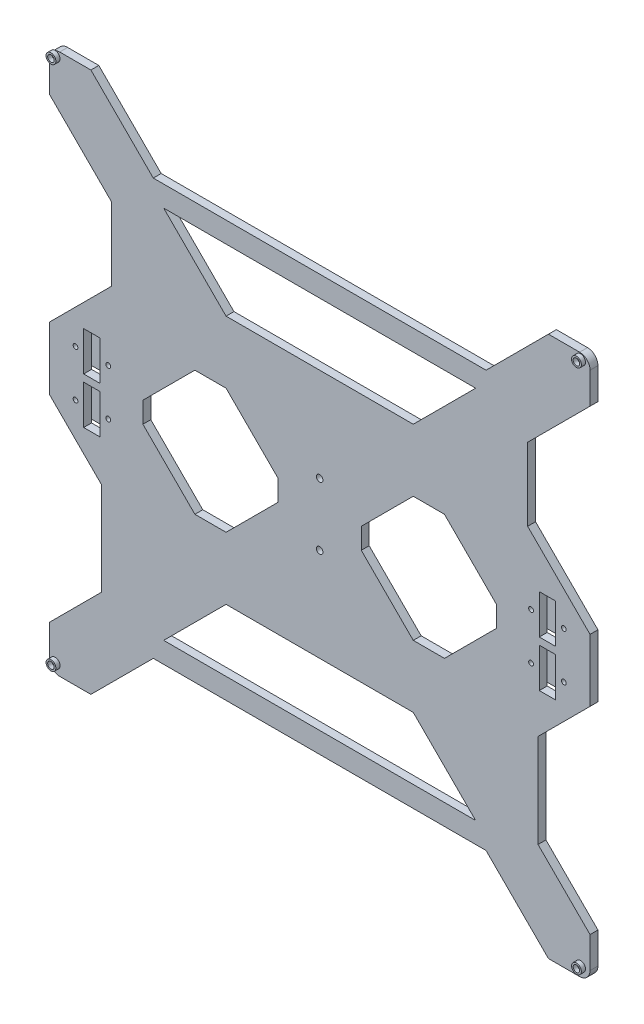
SolidWorks part; units mm, degrees
material "5052-H32"
ref_plane "Front Plane" through (0, 0, 0) normal (0, 0, 1) x (1, 0, 0)
ref_plane "Top Plane" through (0, 0, 0) normal (0, 1, 0) x (1, 0, 0)
ref_plane "Right Plane" through (0, 0, 0) normal (1, 0, 0) x (0, 0, -1)
sketch "Model" plane through (0, 0, 0) normal (0, 0, 1) x (1, 0, 0)
  line L0 (38.5361, 132.6139) -> (38.5361, 132.4727)
  line L1 (38.5361, -178.6774) -> (38.5361, -178.7219)
  line L2 (-253.5639, -197.5861) -> (-253.5639, -197.7273)
  line L3 (-252.5813, 70.3317) -> (-252.5813, 25.8817)
  line L4 (-258.9313, -82.0683) -> (-258.9313, -139.2183)
  line L5 (38.5361, 132.6139) -> (38.5361, 132.4727)
  line L6 (38.5361, -178.6774) -> (38.5361, -178.7219)
  line L7 (7.7687, -139.2183) -> (7.7687, -82.0683)
  line L8 (1.4187, 25.8817) -> (1.4187, 70.3317)
  line L9 (-23.9813, 95.7317) -> (-227.1813, 95.7317)
  line L10 (-290.6813, 108.4317) -> (-252.5813, 70.3317)
  line L11 (-30.3313, -145.5683) -> (-68.4313, -107.4683)
  line L12 (-23.9813, -158.2683) -> (14.1187, -196.3683)
  line L13 (39.5187, 108.4317) -> (39.5187, 127.4817)
  line L14 (-227.1813, 95.7317) -> (-265.2813, 133.8317)
  line L15 (-220.8313, 83.0317) -> (-182.7313, 44.9317)
  line L16 (-274.6813, -45.4288) -> (-254.6813, -45.4288) construction
  line L17 (39.5187, -170.9683) -> (7.7687, -139.2183)
  line L18 (-265.2813, -196.3683) -> (-227.1813, -158.2683)
  line L19 (-182.7313, -107.4683) -> (-68.4313, -107.4683)
  line L20 (-264.6813, -45.4288) -> (-264.6813, -43.5832) construction
  line L21 (1.4187, 70.3317) -> (39.5187, 108.4317)
  line L22 (-23.9813, 95.7317) -> (14.1187, 133.8317)
  line L23 (-30.3313, 83.0317) -> (-68.4313, 44.9317)
  line L25 (-258.9313, -139.2183) -> (-290.6813, -170.9683)
  line L26 (-182.7313, 44.9317) -> (-68.4313, 44.9317)
  line L27 (-220.8313, -145.5683) -> (-182.7313, -107.4683)
  line L28 (-220.8313, -145.5683) -> (-30.3313, -145.5683)
  line L29 (-258.9313, -82.0683) -> (-290.6813, -50.3183)
  line L30 (-290.6813, -12.2183) -> (-290.6813, -50.3183)
  line L31 (-274.6813, -43.9683) -> (-274.6813, -31.2683) construction
  line L32 (-290.6813, -12.2183) -> (-252.5813, 25.8817)
  line L33 (-201.7813, -69.3683) -> (-233.5313, -37.6183)
  line L34 (-182.7313, -69.3683) -> (-201.7813, -69.3683)
  line L35 (1.4187, 25.8817) -> (39.5187, -12.2183)
  line L36 (39.5187, -12.2183) -> (39.5187, -50.3183)
  line L37 (-150.9813, -37.6183) -> (-182.7313, -69.3683)
  line L38 (39.5187, -50.3183) -> (22.4579, -67.3791)
  line L39 (22.4579, -67.3791) -> (7.7687, -82.0683)
  line L40 (-100.1813, -37.6183) -> (-100.1813, -24.9183)
  line L41 (-150.9813, -37.6183) -> (-150.9813, -24.9183)
  line L42 (-150.9813, -24.9183) -> (-182.7313, 6.8317)
  line L43 (-182.7313, 6.8317) -> (-201.7813, 6.8317)
  line L44 (-201.7813, 6.8317) -> (-233.5313, -24.9183)
  line L45 (-233.5313, -24.9183) -> (-233.5313, -37.6183)
  line L46 (-17.6313, -24.9183) -> (-17.6313, -37.6183)
  line L47 (-49.3813, 6.8317) -> (-17.6313, -24.9183)
  line L48 (-220.8313, 83.0317) -> (-30.3313, 83.0317)
  line L49 (-68.4313, 6.8317) -> (-49.3813, 6.8317)
  line L50 (-100.1813, -24.9183) -> (-68.4313, 6.8317)
  line L51 (-100.1813, -37.6183) -> (-68.4313, -69.3683)
  line L52 (-68.4313, -69.3683) -> (-49.3813, -69.3683)
  line L53 (-49.3813, -69.3683) -> (-17.6313, -37.6183)
  line L58 (-265.2813, -196.3683) -> (-284.3313, -196.3683)
  line L59 (-290.6813, -190.0183) -> (-290.6813, -170.9683)
  line L60 (-290.6813, 108.4317) -> (-290.6813, 127.4817)
  line L61 (-284.3313, 133.8317) -> (-265.2813, 133.8317)
  line L62 (14.1187, 133.8317) -> (33.1687, 133.8317)
  line L64 (39.5187, -170.9683) -> (39.5187, -190.0183)
  line L65 (33.1687, -196.3683) -> (14.1187, -196.3683)
  line L71 (-227.1813, -158.2683) -> (-23.9813, -158.2683)
  line L72 (38.5361, -178.6774) -> (38.5361, -178.7219)
  line L74 (-227.1813, -158.2683) -> (-23.9813, -158.2683)
  line L75 (38.5361, -178.6774) -> (38.5361, -178.7219)
  line L77 (-125.5813, 95.7317) -> (-125.5813, -158.2683) construction
  line L78 (-290.6813, -31.2683) -> (39.5187, -31.2683) construction
  arc A0 (33.1687, -196.3683) -> (39.5187, -190.0183) centre (33.1687, -190.0183) ccw
  arc A1 (-290.6813, -190.0183) -> (-284.3313, -196.3683) centre (-284.3313, -190.0183) ccw
  arc A2 (-290.6813, 127.4817) -> (-284.3313, 133.8317) centre (-284.3313, 127.4817) cw
  arc A3 (33.1687, 133.8317) -> (39.5187, 127.4817) centre (33.1687, 127.4817) cw
  circle A4 centre (-287.1253, -190.6025) radius 1.4605
  circle A5 centre (33.7529, -190.6025) radius 1.4605
  circle A6 centre (33.7529, 130.2757) radius 1.4605
  circle A7 centre (-287.1253, 130.2757) radius 1.4605
  circle A8 centre (-274.6813, -45.4288) radius 1.4605
  circle A9 centre (-254.6813, -45.4288) radius 1.4605
  circle A10 centre (23.5187, -45.4288) radius 1.4605
  circle A11 centre (3.5187, -45.4288) radius 1.4605
  circle A12 centre (23.5187, -17.1078) radius 1.4605
  circle A13 centre (3.5187, -17.1078) radius 1.4605
  circle A14 centre (-254.6813, -17.1078) radius 1.4605
  circle A15 centre (-274.6813, -17.1078) radius 1.4605
  circle A16 centre (-125.5813, -12.2183) radius 2
  circle A17 centre (-125.5813, -50.3183) radius 2
  point P72 (-125.5813, -31.2683)
  point P79 (-290.6813, -31.2683)
  point P114 (-125.5813, 83.0317)
  point P116 (39.5187, -31.2683)
  point P120 (-233.5313, -31.2683)
  point P129 (-150.9813, -31.2683)
  point P141 (-290.6813, -180.4933)
  point P149 (-125.5813, 44.9317)
  point P156 (-17.6313, -31.2683)
  dimension "D28" = 6.35
  dimension "D29" = 6.35
  dimension "D30" = 6.35
  dimension "D31" = 6.35
  dimension "D35" = 2.921
  dimension "D36" = 2.921
  dimension "D37" = 2.921
  dimension "D38" = 2.921
  dimension "D53" = 2.921
  dimension "D54" = 2.921
  dimension "D56" = 4
  dimension "D57" = 4
  dimension "D1" = 330.2
  dimension "D2" = 330.2
  dimension "D3" = 135
  dimension "D4" = 135
  dimension "D5" = 38.1
  dimension "D6" = 135
  dimension "D7" = 135
  dimension "D8" = 19.05
  dimension "D9" = 135
  dimension "D10" = 19.05
  dimension "D11" = 31.75
  dimension "D12" = 190.5
  dimension "D13" = 114.3
  dimension "D14" = 38.1
  dimension "D15" = 114.3
  dimension "D16" = 135
  dimension "D17" = 6.35
  dimension "D18" = 38.1
  dimension "D19" = 135
  dimension "D20" = 135
  dimension "D21" = 6.35
  dimension "D22" = 19.05
  dimension "D23" = 25.4
  dimension "D24" = 38.1
  dimension "D25" = 135
  dimension "D26" = 135
  dimension "D27" = 127
  dimension "D32" = 19.05
  dimension "D33" = 19.05
  dimension "D34" = 19.05
  dimension "D39" = 38.1
  dimension "D40" = 19.05
  dimension "D41" = 38.1
  dimension "D42" = 38.1
  dimension "D43" = 135
  dimension "D44" = 19.05
  dimension "D45" = 31.75
  dimension "D46" = 135
  dimension "D47" = 320.8782
  dimension "D48" = 320.8782
  dimension "D49" = 3.556
  dimension "D50" = 3.556
  dimension "D51" = 20
  dimension "D52" = 26
  dimension "D55" = 12.7
  dimension "D58" = 38.1
  dimension "D59" = 19.05
extrude "Boss-Extrude1" add sketch "Model" along normal mid plane 4.826 contours A3 L62 L22 L9 L14 L61 A2 L60 L10 L3 L32 L30 L29 L4 L25 L59 A1 L58 L18 L71 L12 L65 A0 L64 L17 L7 L39 L38 L36 L35 L8 L21 L13 A17 A16 A14 A13 A12 A10 A9 region at (-125.5808, -32.1456, 0)
sketch "Sketch1" plane through (0, 0, 2.413) normal (0, 0, 1) x (1, 0, 0)
  line L1 (-269.6813, -33.4288) -> (-259.6813, -33.4288)
  line L2 (-269.6813, -33.4288) -> (-269.6813, -57.4288)
  line L3 (-269.6813, -57.4288) -> (-259.6813, -57.4288)
  line L4 (-259.6813, -33.4288) -> (-259.6813, -57.4288)
  line L5 (-269.6813, -5.1078) -> (-259.6813, -5.1078)
  line L6 (-269.6813, -5.1078) -> (-269.6813, -29.1078)
  line L7 (-269.6813, -29.1078) -> (-259.6813, -29.1078)
  line L8 (-259.6813, -5.1078) -> (-259.6813, -29.1078)
  line L9 (8.5187, -5.1078) -> (18.5187, -5.1078)
  line L10 (8.5187, -5.1078) -> (8.5187, -29.1078)
  line L11 (8.5187, -29.1078) -> (18.5187, -29.1078)
  line L12 (18.5187, -5.1078) -> (18.5187, -29.1078)
  line L13 (8.5187, -33.4288) -> (18.5187, -33.4288)
  line L14 (8.5187, -33.4288) -> (8.5187, -57.4288)
  line L15 (8.5187, -57.4288) -> (18.5187, -57.4288)
  line L16 (18.5187, -33.4288) -> (18.5187, -57.4288)
  circle A1 centre (-274.6813, -45.4288) radius 1.4605 construction
  circle A5 centre (-274.6813, -17.1078) radius 1.4605 construction
  circle A7 centre (-254.6813, -17.1078) radius 1.4605 construction
  circle A8 centre (23.5187, -17.1078) radius 1.4605 construction
  circle A9 centre (23.5187, -45.4288) radius 1.4605 construction
  dimension "D3" = 12
  dimension "D4" = 5
  dimension "D5" = 10
  dimension "D8" = 12
  dimension "D11" = 12
  dimension "D15" = 12
  dimension "D1" = 10
  dimension "D2" = 24
  dimension "D6" = 24
  dimension "D7" = 5
  dimension "D9" = 24
  dimension "D10" = 5
  dimension "D12" = 10
  dimension "D13" = 10
  dimension "D14" = 24
  dimension "D16" = 5
extrude "Cut-Extrude1" cut sketch "Sketch1" against normal blind 10
sketch "Sketch2" plane through (0, 0, 2.413) normal (0, 0, 1) x (1, 0, 0)
  circle A0 centre (33.7529, -190.6025) radius 3
  circle A1 centre (33.7529, -190.6025) radius 2
  circle A2 centre (-287.1253, -190.6025) radius 2
  circle A3 centre (-287.1253, -190.6025) radius 3
  circle A4 centre (-287.1253, 130.2757) radius 2
  circle A5 centre (-287.1253, 130.2757) radius 3
  circle A6 centre (33.7529, 130.2757) radius 2
  circle A7 centre (33.7529, 130.2757) radius 3
  dimension "D1" = 6
  dimension "D2" = 4
extrude "Boss-Extrude2" add sketch "Sketch2" along normal blind 2.54
sketch "Sketch3" plane through (0, 0, -2.413) normal (0, 0, -1) x (-1, 0, 0)
  line L0 (264.6813, -5.1078) -> (264.6813, -17.1078) construction
  line L1 (254.6813, -7.1078) -> (274.6813, -7.1078)
  line L2 (254.6813, -7.1078) -> (254.6813, -27.1078)
  line L3 (254.6813, -27.1078) -> (274.6813, -27.1078)
  line L4 (274.6813, -7.1078) -> (274.6813, -27.1078)
  line L5 (254.6813, -7.1078) -> (274.6813, -27.1078) construction
  line L6 (254.6813, -27.1078) -> (274.6813, -7.1078) construction
  line L7 (254.6813, -27.1078) -> (274.6813, -27.1078)
  line L12 (254.6813, -35.4288) -> (274.6813, -35.4288)
  line L13 (113.0267, 3.6533) -> (134.9991, 3.6533)
  line L14 (113.0267, 3.6533) -> (113.0267, -64.6419)
  line L15 (113.0267, -64.6419) -> (134.9991, -64.6419)
  line L16 (134.9991, 3.6533) -> (134.9991, -64.6419)
  line L17 (113.0267, 3.6533) -> (134.9991, -64.6419) construction
  line L18 (113.0267, -64.6419) -> (134.9991, 3.6533) construction
  line L19 (-23.5187, -7.1078) -> (-3.5187, -7.1078)
  line L20 (-23.5187, -7.1078) -> (-23.5187, -27.1078)
  line L22 (-3.5187, -7.1078) -> (-3.5187, -27.1078)
  line L23 (-23.5187, -7.1078) -> (-3.5187, -27.1078) construction
  line L24 (-23.5187, -27.1078) -> (-3.5187, -7.1078) construction
  line L29 (-3.5187, -27.1078) -> (-23.5187, -27.1078)
  line L30 (254.6813, -35.4288) -> (254.6813, -55.4288)
  line L31 (259.6813, -5.1078) -> (269.6813, -5.1078) construction
  line L32 (264.6813, -17.1078) -> (269.6813, -17.1078) construction
  line L33 (269.6813, -5.1078) -> (269.6813, -29.1078) construction
  line L34 (264.6813, -33.4288) -> (264.6813, -45.4288) construction
  line L35 (259.6813, -33.4288) -> (269.6813, -33.4288) construction
  line L36 (264.6813, -45.4288) -> (269.6813, -45.4288) construction
  line L37 (269.6813, -33.4288) -> (269.6813, -57.4288) construction
  line L38 (-13.5187, -5.1078) -> (-13.5187, -17.1078) construction
  line L39 (-18.5187, -5.1078) -> (-8.5187, -5.1078) construction
  line L40 (-13.5187, -17.1078) -> (-8.5187, -17.1078) construction
  line L41 (-8.5187, -5.1078) -> (-8.5187, -29.1078) construction
  line L42 (-13.5187, -33.4288) -> (-13.5187, -45.4288) construction
  line L43 (-18.5187, -33.4288) -> (-8.5187, -33.4288) construction
  line L44 (-13.5187, -45.4288) -> (-8.5187, -45.4288) construction
  line L45 (-8.5187, -33.4288) -> (-8.5187, -57.4288) construction
  line L46 (-23.5187, -35.4288) -> (-3.5187, -35.4288)
  line L47 (-23.5187, -35.4288) -> (-23.5187, -55.4288)
  line L48 (-23.5187, -55.4288) -> (-3.5187, -55.4288)
  line L49 (-3.5187, -35.4288) -> (-3.5187, -55.4288)
  line L50 (-23.5187, -35.4288) -> (-3.5187, -55.4288) construction
  line L51 (-23.5187, -55.4288) -> (-3.5187, -35.4288) construction
  line L52 (254.6813, -55.4288) -> (274.6813, -55.4288)
  line L53 (274.6813, -35.4288) -> (274.6813, -55.4288)
  line L54 (254.6813, -35.4288) -> (274.6813, -55.4288) construction
  line L55 (254.6813, -55.4288) -> (274.6813, -35.4288) construction
  point P0 (264.6813, -17.1078)
  point P5 (264.6813, -45.4288)
  point P8 (124.0129, -30.4943)
  point P13 (-13.5187, -17.1078)
  point P18 (-13.5187, -45.4288)
  dimension "D1" = 20
  dimension "D2" = 20
  dimension "D3" = 20
  dimension "D4" = 20
  dimension "D5" = 20
  dimension "D6" = 20
  dimension "D7" = 20
  dimension "D8" = 20
extrude "Boss-Extrude3" add sketch "Sketch3" along normal blind 1 contours L29 L22 L19 L20 | L49 L46 L47 L48 | L4 L1 L2 L3 | L53 L12 L30 L52 | L16 L13 L14 L15 region at (-264.6813, -17.1078, -2.413) region at (-264.6813, -45.4288, -2.413) region at (-124.0129, -30.4943, -2.413) region at (13.5187, -17.1078, -2.413) region at (13.5187, -45.4288, -2.413)
